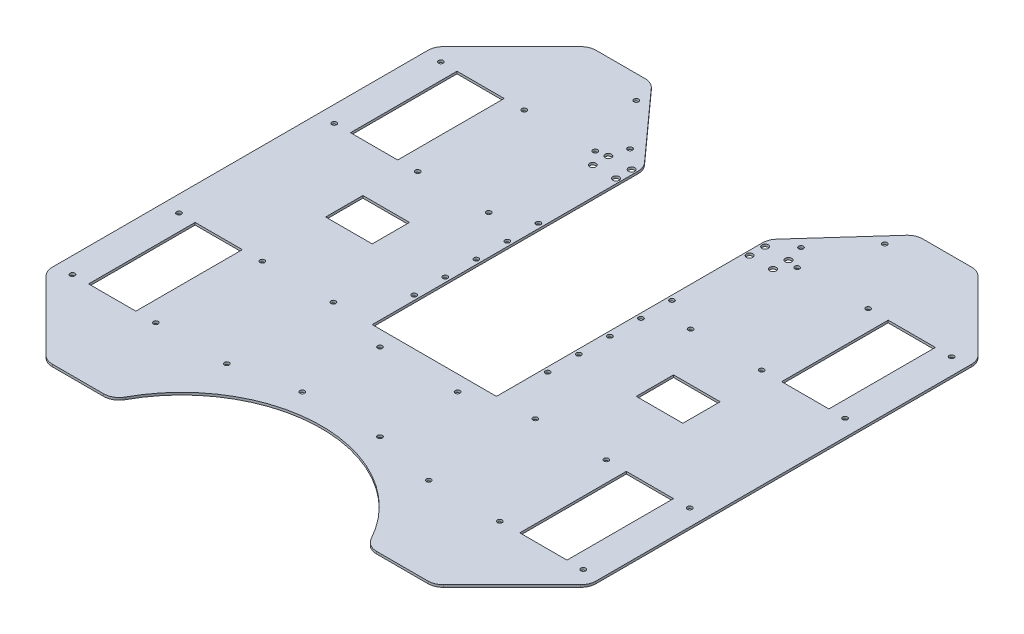
SolidWorks part; units mm, degrees
material "PMMA"
ref_plane "前视基准面" through (0, 0, 0) normal (0, 0, 1) x (1, 0, 0)
ref_plane "上视基准面" through (0, 0, 0) normal (0, 1, 0) x (1, 0, 0)
ref_plane "右视基准面" through (0, 0, 0) normal (1, 0, 0) x (0, 0, -1)
other "Configuration Table"
sketch "草图1" plane through (0, 0, 0) normal (0, 1, 0) x (1, 0, 0)
  line L0 (-125, 175) -> (-175, 125)
  line L1 (125, -175) -> (81.7103, -175)
  line L2 (175, -125) -> (175, 125)
  line L3 (125, 175) -> (85, 175)
  line L4 (-175, -125) -> (-175, 125)
  line L5 (-85, 175) -> (-40, 125)
  line L7 (125, 175) -> (175, 125)
  line L8 (175, -125) -> (125, -175)
  line L9 (-125, -175) -> (-175, -125)
  line L10 (40, 125) -> (85, 175)
  line L11 (-85, 175) -> (-125, 175)
  line L12 (40, 125) -> (40, 85)
  line L13 (40, 85) -> (-40, 85)
  line L14 (-40, 85) -> (-40, 125)
  line L15 (-153.994, 50) -> (-123.594, 50)
  line L16 (-123.594, 50) -> (-123.594, 118.58)
  line L17 (-123.594, 118.58) -> (-153.994, 118.58)
  line L18 (-153.994, 118.58) -> (-153.994, 50)
  line L19 (123.594, 50) -> (153.994, 50)
  line L20 (153.994, 50) -> (153.994, 118.58)
  line L21 (153.994, 118.58) -> (123.594, 118.58)
  line L22 (123.594, 118.58) -> (123.594, 50)
  line L23 (-175, 0) -> (175, 0) construction
  line L24 (-123.594, -118.58) -> (-153.994, -118.58)
  line L25 (-123.594, -50) -> (-123.594, -118.58)
  line L26 (-153.994, -50) -> (-123.594, -50)
  line L27 (-153.994, -118.58) -> (-153.994, -50)
  line L28 (153.994, -118.58) -> (123.594, -118.58)
  line L29 (153.994, -50) -> (153.994, -118.58)
  line L30 (123.594, -50) -> (153.994, -50)
  line L31 (123.594, -118.58) -> (123.594, -50)
  line L32 (-81.7103, -175) -> (-125, -175)
  line L33 (-80, 160) -> (-55, 131) construction
  line L34 (0, 85) -> (0, -124.4881) construction
  line L35 (-40, 85) -> (-40, -25)
  line L36 (-40, -25) -> (40, -25)
  line L37 (40, -25) -> (40, 85)
  circle A0 centre (-55, 131) radius 1.55
  circle A1 centre (-80, 160) radius 1.55
  circle A2 centre (55, 131) radius 1.55
  circle A3 centre (80, 160) radius 1.55
  circle A4 centre (-65, 118.58) radius 1.55
  circle A5 centre (-65, 50) radius 1.55
  circle A6 centre (-110.72, 50) radius 1.55
  circle A7 centre (-110.72, 118.58) radius 1.55
  circle A12 centre (-164.434, 118.58) radius 1.55
  circle A13 centre (-164.434, 50) radius 1.55
  circle A14 centre (-65, -118.58) radius 1.55
  circle A15 centre (-65, -50) radius 1.55
  circle A16 centre (-110.72, -50) radius 1.55
  circle A17 centre (-110.72, -118.58) radius 1.55
  circle A18 centre (-164.434, -50) radius 1.55
  circle A19 centre (-164.434, -118.58) radius 1.55
  circle A20 centre (65, 50) radius 1.55
  circle A21 centre (110.72, 50) radius 1.55
  circle A22 centre (110.72, 118.58) radius 1.55
  circle A23 centre (65, 118.58) radius 1.55
  circle A24 centre (164.434, 118.58) radius 1.55
  circle A25 centre (164.434, 50) radius 1.55
  circle A26 centre (164.434, -118.58) radius 1.55
  circle A27 centre (164.434, -50) radius 1.55
  circle A28 centre (110.72, -50) radius 1.55
  circle A29 centre (110.72, -118.58) radius 1.55
  circle A30 centre (65, -118.58) radius 1.55
  circle A31 centre (65, -50) radius 1.55
  arc A32 (-81.7103, -175) -> (81.7103, -175) centre (0, -212.7283) cw
  circle A33 centre (25, -60) radius 1.55
  circle A34 centre (25, -110) radius 1.55
  circle A35 centre (-25, -60) radius 1.55
  circle A36 centre (-25, -110) radius 1.55
  circle A37 centre (-43, 120) radius 2.05
  circle A38 centre (-43, 110) radius 2.05
  circle A39 centre (-58, 110) radius 2.05
  circle A40 centre (-58, 120) radius 2.05
  circle A41 centre (43, 120) radius 2.05
  circle A42 centre (58, 120) radius 2.05
  circle A43 centre (58, 110) radius 2.05
  circle A44 centre (43, 110) radius 2.05
  circle A45 centre (43, -20) radius 1.55
  circle A46 centre (43, 0) radius 1.55
  circle A47 centre (43, 20) radius 1.55
  circle A48 centre (43, 40) radius 1.55
  circle A49 centre (43, 60) radius 1.55
  circle A50 centre (-43, -20) radius 1.55
  circle A51 centre (-43, 0) radius 1.55
  circle A52 centre (-43, 20) radius 1.55
  circle A53 centre (-43, 40) radius 1.55
  circle A54 centre (-43, 60) radius 1.55
  point P0 (0, 0)
  point P1 (-85, 175)
  point P2 (85, 175)
  point P3 (40, 125)
  point P4 (-40, 125)
  point P6 (125, 175)
  point P8 (175, 125)
  point P10 (175, -125)
  point P11 (125, -175)
  point P12 (-125, -175)
  point P13 (-175, -125)
  point P24 (-80, 160)
  point P25 (-55, 131)
  point P26 (55, 131)
  point P27 (80, 160)
  point P36 (-164.434, 118.58)
  point P37 (-164.434, 50)
  point P38 (-153.994, 118.58)
  point P39 (-123.594, 50)
  point P40 (-110.72, 118.58)
  point P41 (-110.72, 50)
  point P42 (-65, 118.58)
  point P43 (-65, 50)
  point P47 (-123.594, 118.58)
  point P53 (-153.994, 50)
  point P66 (-40, 85)
  point P67 (40, 85)
  point P70 (110.72, 50)
  point P71 (65, 50)
  point P72 (123.594, 50)
  point P73 (153.994, 50)
  point P74 (164.434, 50)
  point P75 (65, 118.58)
  point P76 (110.72, 118.58)
  point P77 (123.594, 118.58)
  point P78 (153.994, 118.58)
  point P81 (164.434, 118.58)
  point P85 (-65, -118.58)
  point P88 (-65, -50)
  point P91 (-110.72, -50)
  point P94 (-110.72, -118.58)
  point P101 (-164.434, -50)
  point P104 (-164.434, -118.58)
  point P118 (164.434, -118.58)
  point P121 (164.434, -50)
  point P128 (110.72, -50)
  point P131 (110.72, -118.58)
  point P134 (65, -118.58)
  point P137 (65, -50)
  point P157 (58, 110)
  point P158 (43, 110)
  point P159 (43, 120)
  point P160 (58, 120)
  point P189 (-43, 60)
  dimension "D29" = 3.1
  dimension "D30" = 3.1
  dimension "D31" = 3.1
  dimension "D32" = 3.1
  dimension "D40" = 3.1
  dimension "D41" = 3.1
  dimension "D42" = 3.1
  dimension "D43" = 3.1
  dimension "D44" = 3.1
  dimension "D45" = 3.1
  dimension "D46" = 3.1
  dimension "D47" = 3.1
  dimension "D48" = 3.1
  dimension "D49" = 3.1
  dimension "D60" = 3.1
  dimension "D61" = 3.1
  dimension "D62" = 43.2897
  dimension "D63" = 90
  dimension "D67" = 3.1
  dimension "D68" = 3.1
  dimension "D69" = 3.1
  dimension "D70" = 3.1
  dimension "D75" = 4.1
  dimension "D76" = 4.1
  dimension "D77" = 4.1
  dimension "D78" = 4.1
  dimension "D80" = 110
  dimension "D83" = 5
  dimension "D85" = 20
  dimension "D1" = 175
  dimension "D2" = 175
  dimension "D3" = 125
  dimension "D4" = 125
  dimension "D5" = 125
  dimension "D6" = 125
  dimension "D7" = 125
  dimension "D8" = 125
  dimension "D9" = 125
  dimension "D10" = 125
  dimension "D11" = 175
  dimension "D12" = 175
  dimension "D13" = 40
  dimension "D14" = 40
  dimension "D15" = 85
  dimension "D16" = 85
  dimension "D17" = 125
  dimension "D18" = 125
  dimension "D19" = 40
  dimension "D20" = 45
  dimension "D21" = 160
  dimension "D22" = 160
  dimension "D23" = 80
  dimension "D24" = 80
  dimension "D25" = 55
  dimension "D26" = 131
  dimension "D27" = 55
  dimension "D28" = 131
  dimension "D33" = 50
  dimension "D34" = 118.58
  dimension "D35" = 65
  dimension "D36" = 45.72
  dimension "D37" = 12.874
  dimension "D38" = 30.4
  dimension "D39" = 10.44
  dimension "D50" = 40
  dimension "D51" = 40
  dimension "D52" = 85
  dimension "D53" = 85
  dimension "D54" = 138.013
  dimension "D55" = 65
  dimension "D56" = 45.72
  dimension "D57" = 12.874
  dimension "D58" = 30.4
  dimension "D59" = 10.44
  dimension "D64" = 0
  dimension "D65" = 25
  dimension "D66" = 25
  dimension "D71" = 60
  dimension "D72" = 50
  dimension "D73" = 15
  dimension "D74" = 10
  dimension "D79" = 43
  dimension "D81" = 120
  dimension "D82" = 110
  dimension "D84" = 3
  dimension "D86" = 20
  dimension "D87" = 20
  dimension "D88" = 20
extrude "凸台-拉伸1" add sketch "草图1" along normal blind 1.5 contours A1 | A0 | L8 L1 A32 L32 L9 L4 L0 L11 L5 L14 L13 L12 L10 L3 L7 L2 | A5 | A3 | A2 | A4 | A7 | A12 | L16 L17 L18 L15 | A6 | L21 L22 L19 L20 | A13 | A16 | A17 | A14 | A15 | A18 | A19 | L25 L24 L27 L26 | A20 | A21 | A22 | A23 | A24 | A25 | A28 | A26 | A27 | L28 L31 L30 L29 | A30 | A31 | A29 | A35 | A36 | A33 | A34 | A39 | A40 | A37 | A38 | A43 | A42 | A41 | A44
fillet "圆角1" radius 10 1 edges at (-40, 0.75, -125)
fillet "圆角2" radius 10 1 edges at (40, 0.75, -125)
fillet "圆角3" radius 10 12 edges at (-85, 0.75, -175) (85, 0.75, -175) (125, 0.75, -175) (175, 0.75, -125) (175, 0.75, 125) (125, 0.75, 175) (81.7103, 0.75, 175) (-81.7103, 0.75, 175) (-125, 0.75, 175) (-175, 0.75, 125) (-175, 0.75, -125) (-125, 0.75, -175)
sketch "草图2" plane through (0, 1.5, 0) normal (0, 1, 0) x (1, 0, 0)
  line L1 (-40, 85) -> (40, 85)
  line L2 (-40, 85) -> (-40, -50)
  line L3 (-40, -50) -> (40, -50)
  line L4 (40, 85) -> (40, -50)
  dimension "D1" = 80
  dimension "D2" = 135
extrude "切除-拉伸1" cut sketch "草图2" against normal blind 10
sketch "草图3" plane through (0, 1.5, 0) normal (0, 1, 0) x (1, 0, 0)
  line L0 (-87.875, -175) -> (-120.8579, -175) construction
  line L1 (-115, 19) -> (-85, 19)
  line L2 (-115, 19) -> (-115, -5)
  line L3 (-115, -5) -> (-85, -5)
  line L4 (-85, 19) -> (-85, -5)
  line L5 (-175, -120.8579) -> (-175, 120.8579) construction
  line L6 (120.8579, -175) -> (87.875, -175) construction
  line L7 (85, 19) -> (115, 19)
  line L8 (85, 19) -> (85, -5)
  line L9 (85, -5) -> (115, -5)
  line L10 (115, 19) -> (115, -5)
  line L11 (175, -120.8579) -> (175, 120.8579) construction
  dimension "D1" = 30
  dimension "D2" = 24
  dimension "D3" = 170
  dimension "D4" = 60
  dimension "D5" = 30
  dimension "D6" = 24
  dimension "D7" = 170
  dimension "D8" = 60
extrude "切除-拉伸2" cut sketch "草图3" against normal blind 10
extrude "切除-拉伸3" cut sketch "草图1<4>" along normal blind 10 contours A54 | A53 | A52 | A51 | A50 | A49 | A48 | A47 | A46 | A45
sketch "草图1<4>" plane through (0, 0, 0) normal (0, 1, 0) x (1, 0, 0) same geometry as "草图1"
